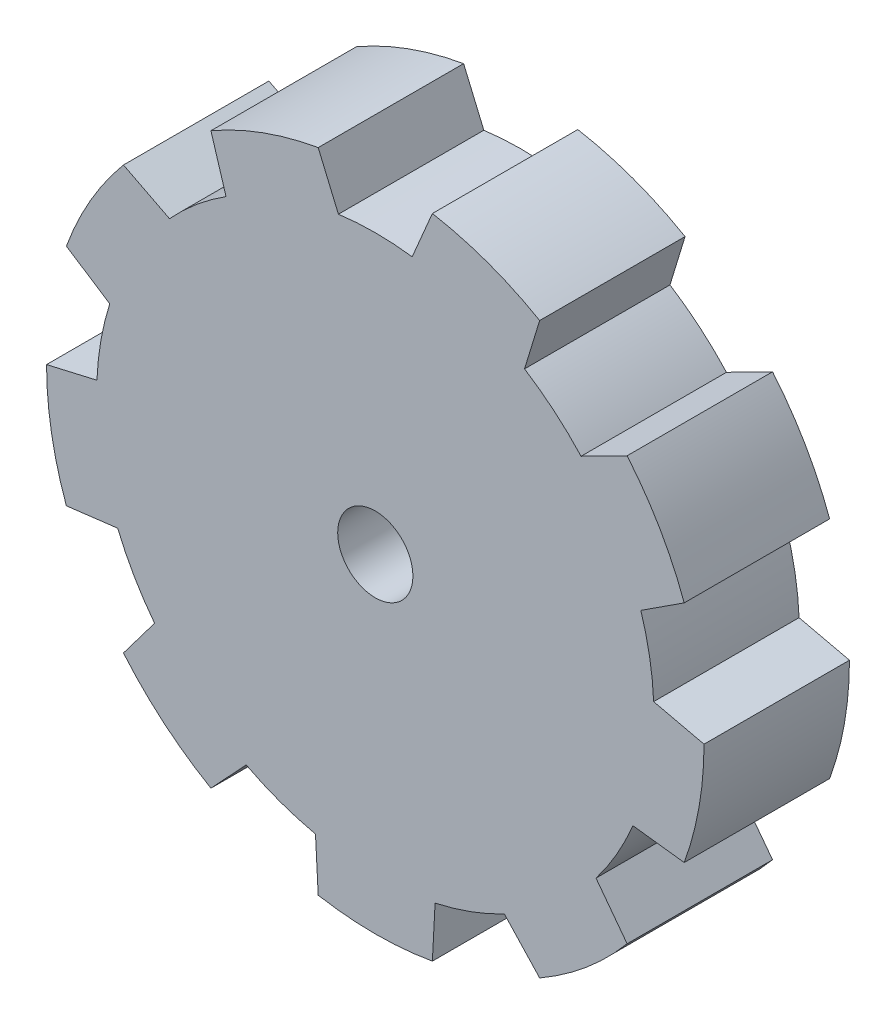
SolidWorks part; units mm, degrees
ref_plane "Front Plane" through (0, 0, 0) normal (0, 0, 1) x (1, 0, 0)
ref_plane "Top Plane" through (0, 0, 0) normal (0, 1, 0) x (1, 0, 0)
ref_plane "Right Plane" through (0, 0, 0) normal (1, 0, 0) x (0, 0, -1)
sketch "Sketch1" plane through (0, 0, 0) normal (0, 0, 1) x (1, 0, 0)
  circle A0 centre (0, 0) radius 33.3019
extrude "Boss-Extrude1" add sketch "Sketch1" along normal blind 14.732
sketch "Sketch2" plane through (0, 0, 0) normal (0, 0, -1) x (-1, 0, 0)
  line L0 (-0.0453, 0) -> (26.5373, 0) construction
  line L1 (-0.0011, -0.0004) -> (22.253, 8.0994) construction
  line L2 (0, 0) -> (18.0392, 15.1367) construction
  line L3 (33.3019, 0) -> (28.1973, 1.1785)
  line L4 (31.2936, 11.3899) -> (26.8999, 8.5366)
  circle A0 centre (0, 0) radius 28.2219 construction
  circle A1 centre (0, 0) radius 33.3019 construction
  arc A2 (28.1973, 1.1785) -> (26.8999, 8.5366) centre (0, 0) ccw
  arc A3 (33.3019, 0) -> (31.2936, 11.3899) centre (0, 0) ccw
  dimension "D3" = 5.08
  dimension "D1" = 20
  dimension "D2" = 20
  dimension "D4" = 13
  dimension "D5" = 13
extrude "Cut-Extrude1" cut sketch "Sketch2" against normal blind 14.732
pattern_circular "CirPattern1" count 9 every 40 about axis through (0, 0, 14.732) along (0, 0, -1) of "Cut-Extrude1"
sketch "Sketch3" plane through (0, 0, 0) normal (0, 0, -1) x (-1, 0, 0)
  circle A0 centre (0, 0) radius 3.81
  dimension "D1" = 7.62
extrude "Cut-Extrude2" cut sketch "Sketch3" against normal up to next
